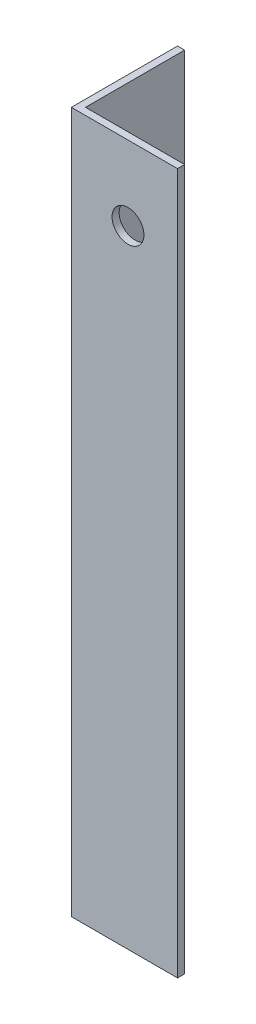
SolidWorks part; units mm, degrees
material "1060 Сплав"
ref_plane "Спереди" through (0, 0, 0) normal (0, 0, 1) x (1, 0, 0)
ref_plane "Сверху" through (0, 0, 0) normal (0, 1, 0) x (1, 0, 0)
ref_plane "Справа" through (0, 0, 0) normal (1, 0, 0) x (0, 0, -1)
sketch "Эскиз1" plane through (0, 0, 0) normal (0, 1, 0) x (1, 0, 0)
  line L0 (0, 0) -> (0, 15)
  line L1 (0, 15) -> (1, 15)
  line L2 (1, 15) -> (1, 1)
  line L3 (1, 1) -> (15, 1)
  line L4 (15, 1) -> (15, 0)
  line L5 (15, 0) -> (0, 0)
  dimension "D1" = 1
  dimension "D2" = 15
extrude "Бобышка-Вытянуть1" add sketch "Эскиз1" along normal blind 99
sketch "Эскиз2" plane through (0, 0, -1) normal (0, 0, -1) x (-1, 0, 0)
  line L0 (-8, 0) -> (-8, 99) construction
  line L1 (-15, 0) -> (-1, 0) construction
  line L2 (-15, 99) -> (-1, 99) construction
  circle A0 centre (-8, 88.5) radius 2.25
  dimension "D1" = 4.5
  dimension "D3" = 10.5
extrude "Вырез-Вытянуть1" cut sketch "Эскиз2" against normal through all
